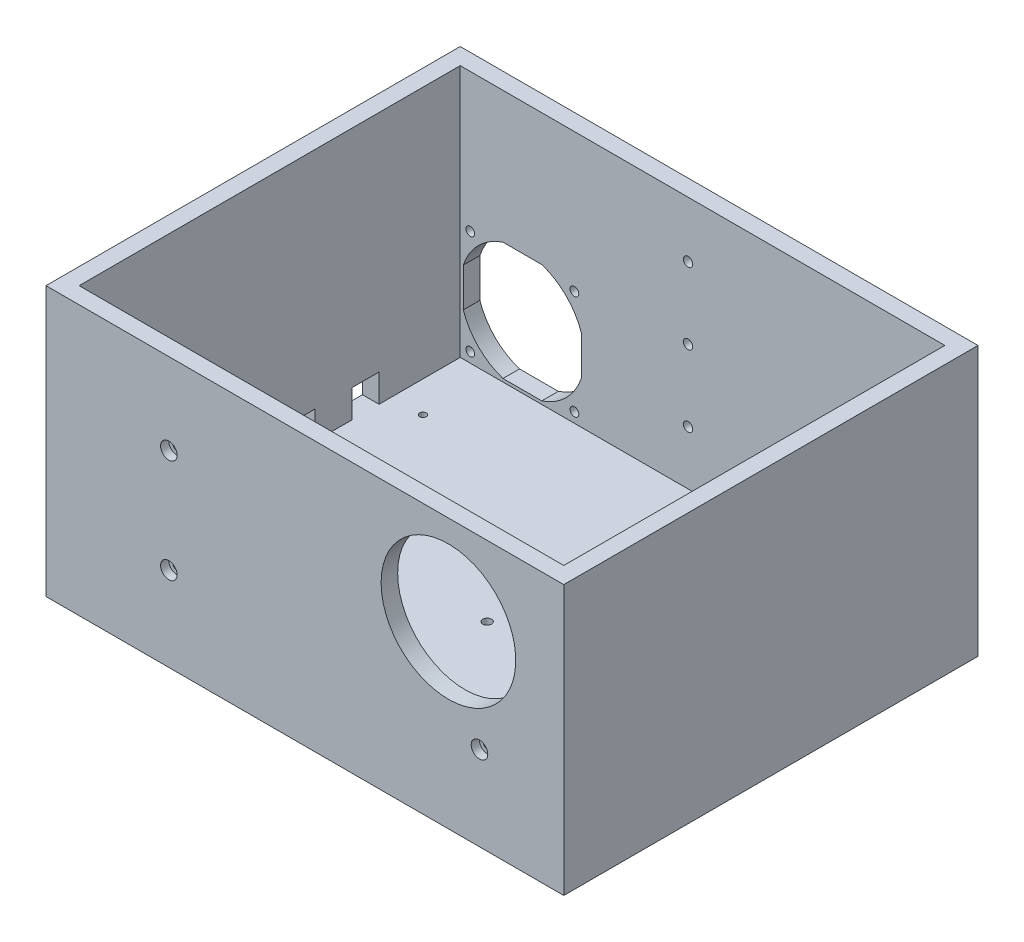
SolidWorks part; units mm, degrees
ref_plane "前基準面" through (0, 0, 0) normal (0, 0, 1) x (1, 0, 0)
ref_plane "上基準面" through (0, 0, 0) normal (0, 1, 0) x (1, 0, 0)
ref_plane "右基準面" through (0, 0, 0) normal (1, 0, 0) x (0, 0, -1)
sketch "草圖1" plane through (0, 0, 0) normal (0, 1, 0) x (1, 0, 0)
  line L1 (-125, -100) -> (125, -100)
  line L2 (-125, -100) -> (-125, 100)
  line L3 (-125, 100) -> (125, 100)
  line L4 (125, -100) -> (125, 100)
  line L5 (-125, -100) -> (125, 100) construction
  line L6 (-125, 100) -> (125, -100) construction
  point P0 (0, 0)
  dimension "D1" = 250
  dimension "D2" = 200
extrude "填料-伸長1" add sketch "草圖1" along normal blind 130
shell "薄殼1" thickness 8 removed face at (0, 130, 0)
sketch "草圖2" plane through (0, 0, 92) normal (0, 0, -1) x (-1, 0, 0)
  line L0 (-117, 8) -> (117, 8) construction
  line L1 (98.2, 8.2) -> (-116.8, 8.2)
  line L2 (98.2, 8.2) -> (98.2, 123.2)
  line L3 (98.2, 123.2) -> (-116.8, 123.2)
  line L4 (-116.8, 8.2) -> (-116.8, 123.2)
  line L5 (98.2, 8.2) -> (-116.8, 123.2) construction
  line L6 (98.2, 123.2) -> (-116.8, 8.2) construction
  line L7 (-117, 130) -> (-117, 8) construction
  line L9 (65.7, 40.7) -> (-84.3, 40.7)
  line L10 (65.7, 40.7) -> (65.7, 90.7)
  line L11 (65.7, 90.7) -> (-84.3, 90.7)
  line L12 (-84.3, 40.7) -> (-84.3, 90.7)
  line L13 (65.7, 40.7) -> (-84.3, 90.7) construction
  line L14 (65.7, 90.7) -> (-84.3, 40.7) construction
  circle A0 centre (65.7, 90.7) radius 2.15
  circle A1 centre (65.7, 40.7) radius 2.15
  circle A2 centre (-84.3, 40.7) radius 2.15
  circle A3 centre (-84.3, 90.7) radius 2.15
  circle A4 centre (-69.3, 86.7) radius 32.5
  point P0 (-9.3, 65.7)
  point P9 (-9.3, 65.7)
  dimension "D9" = 4.3
  dimension "D10" = 47.5
  dimension "D11" = 36.5
  dimension "D12" = 65
  dimension "D1" = 215
  dimension "D2" = 115
  dimension "D3" = 0.2
  dimension "D4" = 0.2
  dimension "D5" = 150
  dimension "D6" = 50
  dimension "D7" = 32.5
  dimension "D8" = 32.5
extrude "除料-伸長1" cut sketch "草圖2" against normal up to next contours A4 | A0 | A1 | A2
sketch "草圖4" plane through (0, 0, 100) normal (0, 0, 1) x (1, 0, 0)
  circle A1 centre (84.3, 40.7) radius 4
  circle A2 centre (-65.7, 90.7) radius 4
  circle A3 centre (-65.7, 40.7) radius 4
  dimension "D1" = 8
extrude "除料-伸長3" cut sketch "草圖4" against normal blind 4
sketch "草圖3" plane through (0, 8, 0) normal (0, 1, 0) x (1, 0, 0)
  line L0 (-117, -92) -> (117, -92) construction
  line L1 (112, -12) -> (0, -12)
  line L2 (112, -12) -> (112, 10.5)
  line L3 (112, 10.5) -> (0, 10.5)
  line L4 (0, -12) -> (0, 10.5)
  line L5 (112, -12) -> (0, 10.5) construction
  line L6 (112, 10.5) -> (0, -12) construction
  line L9 (117, -92) -> (117, 92) construction
  circle A0 centre (0, 10.5) radius 2.1
  circle A1 centre (0, -12) radius 2.1
  circle A2 centre (112, 10.5) radius 2.1
  circle A3 centre (112, -12) radius 2.1
  point P0 (56, -0.75)
  dimension "D5" = 4.2
  dimension "D1" = 22.5
  dimension "D2" = 112
  dimension "D3" = 80
  dimension "D4" = 5
extrude "除料-伸長2" cut sketch "草圖3" against normal through all contours A1 | A0 | A2 | A3
sketch "草圖5" plane through (0, 0, -100) normal (0, 0, -1) x (-1, 0, 0)
  line L0 (-105, 34) -> (7, 34)
  line L5 (-125, 0) -> (125, 0) construction
  line L6 (-125, 130) -> (-125, 0) construction
  line L7 (7, 68.5) -> (-105, 68.5)
  line L8 (7, 68.5) -> (7, 34)
  line L9 (-105, 103) -> (7, 103)
  circle A0 centre (-105, 34) radius 2.25
  circle A1 centre (7, 34) radius 2.25
  circle A2 centre (-105, 68.5) radius 2.25
  circle A3 centre (7, 68.5) radius 2.25
  circle A4 centre (-105, 103) radius 2.25
  circle A5 centre (7, 103) radius 2.25
  dimension "D2" = 4.5
  dimension "D4" = 20
  dimension "D1" = 112
  dimension "D3" = 34
  dimension "D5" = 34.5
  dimension "D6" = 34.5
extrude "除料-伸長4" cut sketch "草圖5" against normal up to next contours A0 | A1 | A3 | A2 | A4 | A5
sketch "草圖6" plane through (0, 8, 0) normal (0, 1, 0) x (1, 0, 0)
  line L1 (-117, 92) -> (-102, 92)
  line L2 (-117, 92) -> (-117, 59)
  line L3 (-117, 59) -> (-102, 59)
  line L4 (-102, 92) -> (-102, 59)
  line L5 (-102, 59) -> (-19.374, 59)
  line L6 (-102, 59) -> (-102, 10.6638)
  line L7 (-102, 10.6638) -> (-19.374, 10.6638)
  line L8 (-19.374, 59) -> (-19.374, 10.6638)
  circle A0 centre (-102, 59) radius 1.6
  circle A1 centre (-19.374, 10.6638) radius 1.6
  dimension "D3" = 3.2
  dimension "D1" = 15
  dimension "D2" = 33
  dimension "D4" = 82.626
  dimension "D5" = 48.3362
extrude "除料-伸長5" cut sketch "草圖6" against normal through all contours A0 | A1
sketch "草圖7" plane through (-125, 0, 0) normal (-1, 0, 0) x (0, 0, 1)
  line L0 (-92, 130) -> (-92, 8) construction
  line L1 (-52.8, 8) -> (-39.8, 8)
  line L2 (-52.8, 8) -> (-52.8, 21.5)
  line L3 (-52.8, 21.5) -> (-39.8, 21.5)
  line L4 (-39.8, 8) -> (-39.8, 21.5)
  line L5 (-92, 8) -> (92, 8) construction
  line L7 (-21.8, 8) -> (-11.3, 8)
  line L8 (-21.8, 8) -> (-21.8, 21.5)
  line L9 (-21.8, 21.5) -> (-11.3, 21.5)
  line L10 (-11.3, 8) -> (-11.3, 21.5)
  dimension "D1" = 13
  dimension "D2" = 13.5
  dimension "D3" = 39.2
  dimension "D5" = 10.5
  dimension "D6" = 18
extrude "除料-伸長6" cut sketch "草圖7" against normal up to next
sketch "草圖8" plane through (0, 0, -100) normal (0, 0, -1) x (-1, 0, 0)
  line L0 (117, 130) -> (117, 8) construction
  line L1 (57, 8) -> (117, 8)
  line L2 (57, 8) -> (57, 68)
  line L3 (57, 68) -> (117, 68)
  line L4 (117, 8) -> (117, 68)
  line L5 (57, 8) -> (117, 68) construction
  line L6 (57, 68) -> (117, 8) construction
  line L7 (58.5, 9.5) -> (115.5, 9.5)
  line L8 (58.5, 9.5) -> (58.5, 66.5)
  line L9 (58.5, 66.5) -> (115.5, 66.5)
  line L10 (115.5, 9.5) -> (115.5, 66.5)
  line L11 (58.5, 9.5) -> (115.5, 66.5) construction
  line L12 (58.5, 66.5) -> (115.5, 9.5) construction
  line L13 (57, 68) -> (61.85, 68)
  line L14 (57, 68) -> (57, 63.15)
  line L15 (57, 63.15) -> (61.85, 63.15)
  line L16 (61.85, 68) -> (61.85, 63.15)
  line L17 (112.15, 12.85) -> (61.85, 12.85)
  line L18 (112.15, 12.85) -> (112.15, 63.15)
  line L19 (112.15, 63.15) -> (61.85, 63.15)
  line L20 (61.85, 12.85) -> (61.85, 63.15)
  line L21 (112.15, 12.85) -> (61.85, 63.15) construction
  line L22 (112.15, 63.15) -> (61.85, 12.85) construction
  line L23 (-117, 8) -> (117, 8) construction
  arc A0 (77.6325, 66.5) -> (58.5, 47.3675) centre (87, 38) ccw
  circle A1 centre (61.85, 63.15) radius 2.1
  circle A2 centre (112.15, 63.15) radius 2.1
  circle A3 centre (112.15, 12.85) radius 2.1
  circle A4 centre (61.85, 12.85) radius 2.1
  arc A5 (115.5, 47.3675) -> (96.3675, 66.5) centre (87, 38) ccw
  arc A6 (96.3675, 9.5) -> (115.5, 28.6325) centre (87, 38) ccw
  arc A7 (58.5, 28.6325) -> (77.6325, 9.5) centre (87, 38) ccw
  point P0 (87, 38)
  point P5 (87, 38)
  dimension "D6" = 4.2
  dimension "D1" = 60
  dimension "D2" = 60
  dimension "D3" = 1.5
  dimension "D4" = 4.85
  dimension "D5" = 4.85
extrude "除料-伸長7" cut sketch "草圖8" against normal up to next contours L18 A2 L19 | L19 A2 L18 | L19 A1 L16 | L16 A1 L15 | L15 A1 L20 | L20 A1 L19 | L17 A3 L18 | L18 A3 L17 | L20 A4 L17 | L17 A4 L20 | L20 A7 L17 A6 L18 A5 L19 A0 | L17 A7 L7 A6 | L8 A7 L20 A0 | L19 A5 L9 A0 | L18 A6 L10 A5 region at (-60.3196, 38, -100) region at (-60.9587, 64.0413, -100) region at (-60.9587, 62.2587, -100) region at (-87, 38, -100) region at (-62.7413, 64.0413, -100) region at (-62.7413, 62.2587, -100) region at (-87, 64.6804, -100) region at (-87, 11.3196, -100) region at (-62.7413, 13.7413, -100) region at (-61.5529, 12.5529, -100) region at (-112.4471, 63.4471, -100) region at (-111.2587, 62.2587, -100) region at (-113.6804, 38, -100) region at (-111.2587, 13.7413, -100) region at (-112.4471, 12.5529, -100)
